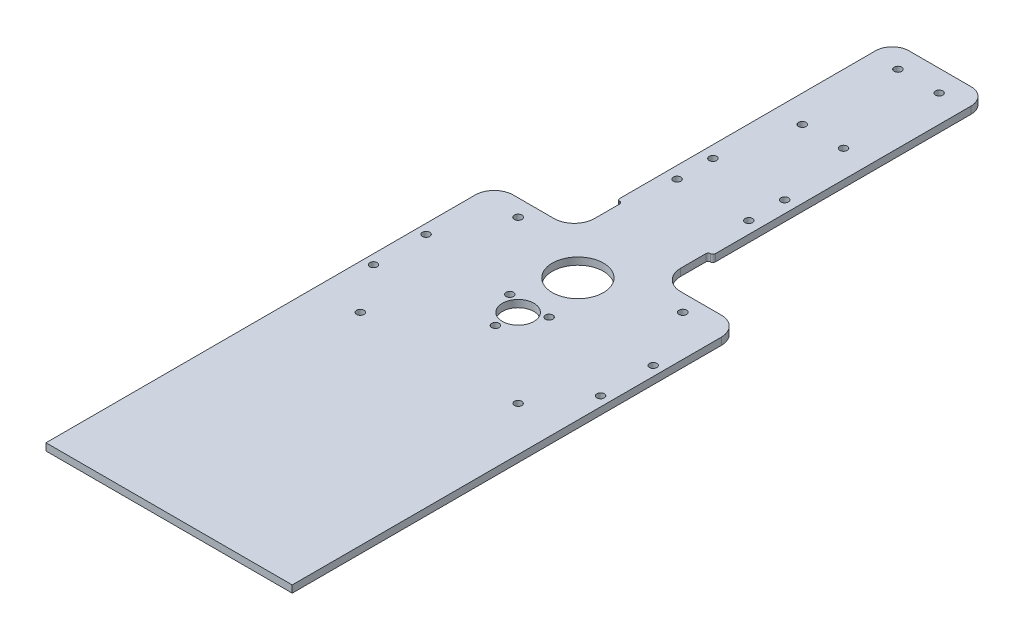
SolidWorks part; units mm, degrees
material "Hexcel AS4C (3000 丝)"
ref_plane "前视基准面" through (0, 0, 0) normal (0, 0, 1) x (1, 0, 0)
ref_plane "上视基准面" through (0, 0, 0) normal (0, 1, 0) x (1, 0, 0)
ref_plane "右视基准面" through (0, 0, 0) normal (1, 0, 0) x (0, 0, -1)
sketch "草图1" plane through (0, 0, 0) normal (0, 1, 0) x (1, 0, 0)
  line L1 (-100, 100) -> (100, 100)
  line L2 (-100, 100) -> (-100, -100)
  line L3 (-100, -100) -> (100, -100)
  line L4 (100, 100) -> (100, -100)
  line L5 (-100, 100) -> (100, -100) construction
  line L6 (-100, -100) -> (100, 100) construction
  point P0 (0, 0)
  dimension "D1" = 200
  dimension "D2" = 200
extrude "凸台-拉伸1" add sketch "草图1" along normal blind 3
sketch "草图2" plane through (0, 3, 0) normal (0, 1, 0) x (1, 0, 0)
  line L0 (0, 0) -> (0, 91) construction
  line L1 (-100, -100) -> (100, -100) construction
  line L2 (100, 100) -> (-100, 100) construction
  line L3 (-100, 0) -> (100, 0) construction
  line L5 (-100, 100) -> (-100, -100) construction
  line L6 (100, -100) -> (100, 100) construction
  line L7 (-29.5, 0) -> (29.5, 0) construction
  line L8 (-10, 100) -> (10, 100) construction
  line L9 (-10, 100) -> (-10, -100) construction
  line L10 (10, 100) -> (10, -100) construction
  line L11 (0, 0) -> (0, -29) construction
  line L13 (0, -29) -> (0, -32) construction
  circle A0 centre (-29.5, 0) radius 22.5 construction
  circle A1 centre (29.5, 0) radius 22.5 construction
  circle A2 centre (0, -29) radius 10.05 construction
  circle A3 centre (29.5, 0) radius 9.5 construction
  circle A4 centre (29.5, 0) radius 8 construction
  circle A5 centre (-29.5, 0) radius 8 construction
  circle A6 centre (-29.5, 0) radius 9.5 construction
  circle A7 centre (29.5, 9.5) radius 1.5
  circle A8 centre (21.5, 0) radius 1.5
  circle A9 centre (29.5, -9.5) radius 1.5
  circle A10 centre (37.5, 0) radius 1.5
  circle A11 centre (-29.5, -9.5) radius 1.5
  circle A12 centre (-37.5, 0) radius 1.5
  circle A13 centre (-21.5, 0) radius 1.5
  circle A14 centre (-29.5, 9.5) radius 1.5
  point P16 (0, 0)
  dimension "D1" = 45
  dimension "D3" = 20.1
  dimension "D4" = 19
  dimension "D5" = 16
  dimension "D6" = 3
  dimension "D7" = 3
  dimension "D2" = 20
  dimension "D9" = 3
  dimension "D10" = 29
extrude "切除-拉伸2" cut sketch "草图2" against normal blind 10
sketch "草图4" plane through (0, 3, 0) normal (0, 1, 0) x (1, 0, 0)
  line L0 (0, 0) -> (0, 91) construction
  line L1 (100, 100) -> (-100, 100) construction
  line L2 (-10, 100) -> (10, 100)
  line L3 (-10, 100) -> (-10, -100) construction
  line L4 (-100, -100) -> (100, -100) construction
  line L5 (10, 100) -> (10, -100) construction
  line L6 (21.5, 0) -> (37.5, 0)
  line L7 (-29.5, 0) -> (0, 0) construction
  line L8 (0, -29) -> (0, 0) construction
  circle A0 centre (0, -29) radius 10.7
  circle A1 centre (29.5, 0) radius 8 construction
  circle A2 centre (29.5, 0) radius 9.5 construction
  circle A3 centre (29.5, 0) radius 22.5 construction
  circle A4 centre (-29.5, 0) radius 9.5 construction
  circle A5 centre (-29.5, 0) radius 8 construction
  circle A6 centre (-29.5, 0) radius 22.5 construction
  dimension "D1" = 21.4
  dimension "D2" = 19
  dimension "D3" = 16
  dimension "D4" = 45
sketch "草图5" plane through (0, 3, 0) normal (0, 1, 0) x (1, 0, 0)
  line L0 (-44.5, -100) -> (-100, -100)
  line L2 (44.5, 0) -> (44.5, -100)
  line L4 (-20, 47.5) -> (-20, 24.995)
  line L6 (-44.5, 0) -> (-44.5, -100)
  line L7 (-100, -100) -> (100, -100) construction
  line L8 (20, 47.5) -> (20, 24.995)
  line L9 (-100, -100) -> (-100, 100)
  line L10 (0, 0) -> (0, 91) construction
  line L11 (0, 47.5) -> (-20, 47.5)
  line L12 (44.5, -100) -> (-44.5, -100)
  line L13 (0, 47.5) -> (20, 47.5)
  line L14 (-100, 100) -> (100, 100)
  line L15 (100, 100) -> (100, -100)
  line L16 (100, -100) -> (44.5, -100)
  arc A0 (29.8, 14.997) -> (44.5, 0) centre (29.5, 0) cw
  arc A1 (20, 24.995) -> (29.8, 14.997) centre (30, 24.995) ccw
  arc A2 (-29.8, 14.997) -> (-44.5, 0) centre (-29.5, 0) ccw
  arc A3 (-20, 24.995) -> (-29.8, 14.997) centre (-30, 24.995) cw
  line M11 (100, -100) -> (100, 100)
  line M12 (100, 100) -> (-100, 100)
  line M13 (-100, 100) -> (-100, -100)
  line M14 (-100, -100) -> (100, -100)
  dimension "D1" = 10
  dimension "D2" = 15
extrude "切除-拉伸3" cut sketch "草图5" against normal blind 10 contours A3 L4 L11 L13 L8 A1 A0 L2 L6 A2 M14 M11 M12 M13 region at (-72.25, 3, 97.1716)
sketch "草图6" plane through (0, 0, 0) normal (0, -1, 0) x (1, 0, 0)
  line L0 (20, -47.5) -> (-20, -47.5) construction
  line L7 (-20, -47.5) -> (-20, -24.995) construction
  circle A1 centre (-15, -42.5) radius 1.55
  circle A2 centre (-15, -27.5) radius 1.55
  circle A3 centre (15, -27.5) radius 1.55
  circle A4 centre (15, -42.5) radius 1.55
  dimension "D1" = 3.1
  dimension "D2" = 5
  dimension "D3" = 5
  dimension "D4" = 30
extrude "φ3.1通孔1" cut sketch "草图6" against normal blind 10
sketch "草图9" plane through (0, 3, 0) normal (0, 1, 0) x (1, 0, 0)
  line L0 (-20, 47.5) -> (-20, 26.3383)
  line L4 (-20, 47.5) -> (20, 47.5)
  line L5 (20, 47.5) -> (20, 26.3383)
  line L8 (12.2609, 20.995) -> (-12.2609, 20.995)
  arc A0 (-18.8003, 24.5054) -> (-13.4605, 21.3948) centre (-29.5, 0) cw
  arc A1 (18.8003, 24.5054) -> (13.4605, 21.3948) centre (29.5, 0) ccw
  arc A2 (18.8003, 24.5054) -> (20, 26.3383) centre (18, 26.3383) ccw
  arc A3 (13.4605, 21.3948) -> (12.2609, 20.995) centre (12.2609, 22.995) cw
  arc A4 (-12.2609, 20.995) -> (-13.4605, 21.3948) centre (-12.2609, 22.995) cw
  arc A5 (-18.8003, 24.5054) -> (-20, 26.3383) centre (-18, 26.3383) cw
  point P20 (-20, 24.995)
  dimension "D1" = 2
sketch "草图11" plane through (0, 3, 0) normal (0, 1, 0) x (1, 0, 0)
  line L0 (44.5, -17.5) -> (44.5, -100)
  line L1 (20, 47.5) -> (20, 7.5)
  line L2 (-44.5, 0) -> (-44.5, -100) construction
  line L3 (-44.5, -17.5) -> (-44.5, -100)
  line L4 (0, 47.5) -> (0, -100) construction
  line L5 (20, 47.5) -> (-20, 47.5) construction
  line L6 (-44.5, -100) -> (44.5, -100) construction
  line L7 (18, -4) -> (18, 6.5)
  line L8 (20, 7.5) -> (19, 7.5)
  line L9 (-39.5, -12.5) -> (-44.5, -12.5)
  line L10 (26.5, -12.5) -> (39.5, -12.5)
  line L11 (20, 47.5) -> (101.1331, 47.5)
  line L12 (101.1331, 47.5) -> (101.1331, -100)
  line L13 (101.1331, -100) -> (44.5, -100)
  line L14 (-20, 47.5) -> (-20, 7.5)
  line L15 (-20, 7.5) -> (-19, 7.5)
  line L16 (-18, -4) -> (-18, 6.5)
  line L17 (-26.5, -12.5) -> (-39.5, -12.5)
  line L18 (-44.5, -12.5) -> (-44.5, -17.5)
  line L19 (-101.1331, -100) -> (-44.5, -100)
  line L20 (-101.1331, 47.5) -> (-101.1331, -100)
  line L21 (-20, 47.5) -> (-101.1331, 47.5)
  line L22 (39.5, -12.5) -> (44.5, -12.5)
  line L23 (44.5, 0) -> (44.5, -100) construction
  line L24 (44.5, -12.5) -> (44.5, -17.5)
  arc A0 (26.5, -12.5) -> (18, -4) centre (26.5, -4) cw
  circle A2 centre (29.5, -9.5) radius 1.5
  circle A4 centre (21.5, 0) radius 1.5
  arc A5 (18, 6.5) -> (19, 7.5) centre (19, 6.5) cw
  arc A6 (-18, 6.5) -> (-19, 7.5) centre (-19, 6.5) ccw
  arc A7 (-26.5, -12.5) -> (-18, -4) centre (-26.5, -4) ccw
  point P21 (-44.5, -12.5)
  dimension "D1" = 8.5
  dimension "D2" = 1
extrude "切除-拉伸6" cut sketch "草图11" against normal up to next
extrude "φ21.4落弹孔" cut sketch "草图4" against normal up to next contours A0 region at (0, 3, 29)
fillet "圆角1" radius 1 2 edges at (-20, 1.5, -7.5) (20, 1.5, -7.5)
sketch "草图12" plane through (0, 0, -47.5) normal (0, 0, -1) x (-1, 0, 0)
  line L0 (-20, 3) -> (-20, 0)
  line L1 (-20, 0) -> (20, 0)
  line L2 (20, 0) -> (20, 3)
  line L3 (20, 3) -> (-20, 3)
extrude "凸台-拉伸2" add sketch "草图12" along normal blind 75
fillet "圆角2" radius 7 2 edges at (-20, 1.5, -122.5) (20, 1.5, -122.5)
sketch "草图13" plane through (0, 3, 0) normal (0, 1, 0) x (1, 0, 0)
  line L0 (-20, 115.5) -> (-20, 8.5) construction
  line L1 (0, 122.5) -> (0, 107.278)
  line L2 (-13, 122.5) -> (13, 122.5) construction
  circle A0 centre (-8.625, 73.5) radius 1.55
  circle A1 centre (-15, 42.5) radius 1.55
  circle A2 centre (-8.625, 113.5) radius 1.55
  circle A3 centre (8.625, 73.5) radius 1.55
  circle A4 centre (8.625, 113.5) radius 1.55
  dimension "D3" = 3.1
  dimension "D5" = 3.1
  dimension "D1" = 31
  dimension "D2" = 11.375
  dimension "D4" = 40
extrude "φ3.1通孔3" cut sketch "草图13" against normal blind 10 contours A2 | A4 | A3 | A0 region at (-8.625, 3, -73.5) region at (-8.625, 3, -113.5) region at (8.625, 3, -73.5) region at (8.625, 3, -113.5)
sketch "草图14" plane through (0, 3, 0) normal (0, 1, 0) x (1, 0, 0)
  line L1 (0, -43) -> (32.1524, -43) construction
  circle A0 centre (0, -29) radius 11 construction
  circle A1 centre (0, -54) radius 9.5 construction
  circle A2 centre (0, -63.5) radius 1.55
  circle A3 centre (-8.2272, -49.25) radius 1.55
  circle A5 centre (8.2272, -49.25) radius 1.55
  circle A6 centre (0, -54) radius 6.6
  point P19 (0, -54)
  dimension "D1" = 22
  dimension "D2" = 25
  dimension "D3" = 19
  dimension "D4" = 3.1
  dimension "D5" = 3
  dimension "D6" = 13.2
extrude "2006电机固定" cut sketch "草图14" against normal up to next
sketch "草图15" plane through (0, 3, 0) normal (0, 1, 0) x (1, 0, 0)
  circle A0 centre (0, -54) radius 32.5 construction
  circle A1 centre (0, -29) radius 11
  circle A2 centre (0, -29) radius 10
  circle A3 centre (0, -49) radius 37
  circle A4 centre (0, -54) radius 35
  circle A5 centre (0, -49) radius 33.5
  circle A6 centre (15, -19.0459) radius 1.5
  circle A7 centre (-15, -19.0459) radius 1.5
  point P12 (0, -15.5)
  dimension "D1" = 65
  dimension "D2" = 22
  dimension "D3" = 20
  dimension "D4" = 74
  dimension "D5" = 70
  dimension "D6" = 67
  dimension "D7" = 3
  dimension "D9" = 15
sketch "草图18" plane through (0, 3, 0) normal (0, 1, 0) x (1, 0, 0)
  line L0 (0, -54) -> (0, -74.1208) construction
  circle A0 centre (33, -87) radius 1.55
  circle A1 centre (-33, -87) radius 1.55
  dimension "D1" = 3.1
  dimension "D2" = 33
  dimension "D3" = 33
extrude "弹仓固定2" cut sketch "草图18" against normal blind 8
sketch "草图19" plane through (0, 0, 100) normal (0, 0, 1) x (1, 0, 0)
  line L0 (-44.5, 3) -> (-44.5, 0)
  line L1 (-44.5, 0) -> (44.5, 0)
  line L2 (44.5, 0) -> (44.5, 3)
  line L3 (44.5, 3) -> (-44.5, 3)
extrude "凸台-拉伸3" add sketch "草图19" along normal blind 100
sketch "草图20" plane through (-44.5, 0, 0) normal (-1, 0, 0) x (0, 0, 1)
  line L0 (12.5, 3) -> (12.5, 0)
  line L1 (12.5, 0) -> (200, 0)
  line L2 (200, 0) -> (200, 3)
  line L3 (200, 3) -> (12.5, 3)
extrude "凸台-拉伸4" add sketch "草图20" along normal blind 7
mirror "镜向2" about plane through (0, 0, 0) normal (1, 0, 0) of "凸台-拉伸4"
fillet "圆角3" radius 8 2 edges at (51.5, 1.5, 12.5) (-51.5, 1.5, 12.5)
sketch "草图17" plane through (0, 3, 0) normal (0, 1, 0) x (1, 0, 0)
  line L1 (-51.5, -200) -> (-51.5, -20.5) construction
  line L2 (0, 0) -> (0, -26.2063) construction
  circle A0 centre (-47.5, -45) radius 1.55
  circle A1 centre (-47.5, -67) radius 1.55
  circle A2 centre (47.5, -67) radius 1.55
  circle A3 centre (47.5, -45) radius 1.55
  dimension "D2" = 3.1
  dimension "D4" = 3.1
  dimension "D1" = 45
  dimension "D3" = 4
  dimension "D5" = 22
extrude "上下板后支撑固定孔" cut sketch "草图17" against normal up to next
sketch "草图16" plane through (0, 3, 0) normal (0, 1, 0) x (1, 0, 0)
  line L0 (0, -54) -> (-34.4467, -19.5533) construction
  line L1 (0, -54) -> (0, -33.1135) construction
  circle A0 centre (0, -54) radius 44 construction
  circle A2 centre (-34.4467, -19.5533) radius 1.6
  circle A3 centre (34.4467, -19.5533) radius 1.6
  dimension "D1" = 88
  dimension "D2" = 3.2
extrude "弹仓固定孔" cut sketch "草图16" against normal up to next
